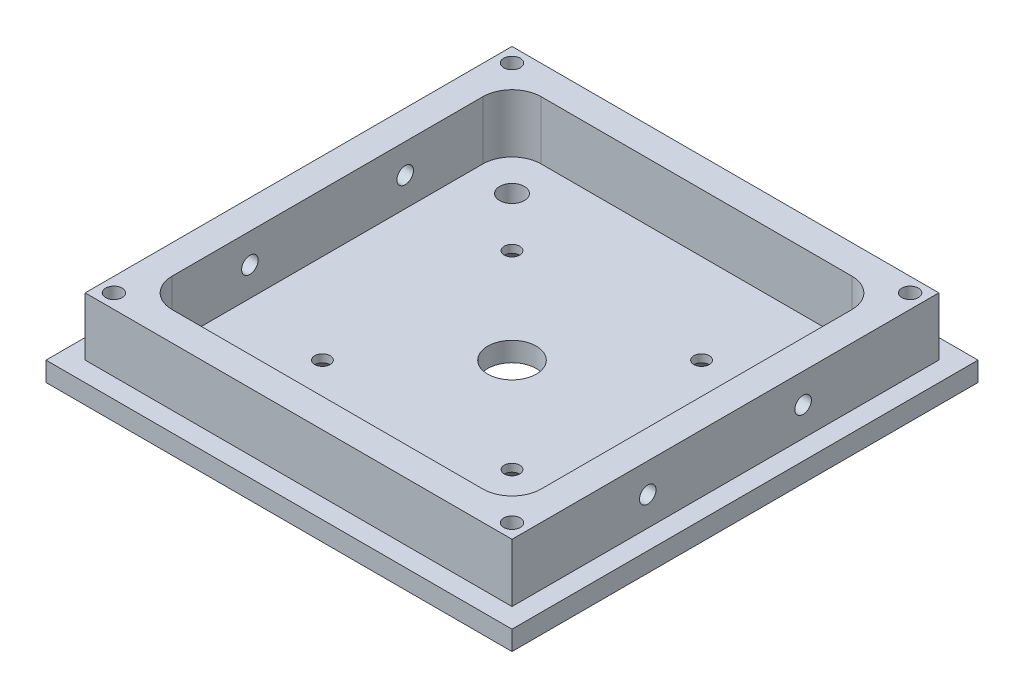
SolidWorks part; units mm, degrees
material "6061-T6 (SS)"
ref_plane "Front Plane" through (0, 0, 0) normal (0, 0, 1) x (1, 0, 0)
ref_plane "Top Plane" through (0, 0, 0) normal (0, 1, 0) x (1, 0, 0)
ref_plane "Right Plane" through (0, 0, 0) normal (1, 0, 0) x (0, 0, -1)
sketch "Sketch1" plane through (0, 0, 0) normal (0, 1, 0) x (1, 0, 0)
  line L1 (-38.1, -38.1) -> (38.1, -38.1)
  line L2 (-38.1, -38.1) -> (-38.1, 38.1)
  line L3 (-38.1, 38.1) -> (38.1, 38.1)
  line L4 (38.1, -38.1) -> (38.1, 38.1)
  line L5 (-38.1, -38.1) -> (38.1, 38.1) construction
  line L6 (-38.1, 38.1) -> (38.1, -38.1) construction
  point P0 (0, 0)
  dimension "D1" = 76.2
  dimension "D2" = 76.2
extrude "Boss-Extrude1" add sketch "Sketch1" along normal blind 3.175
sketch "Sketch2" plane through (0, 3.175, 0) normal (0, 1, 0) x (1, 0, 0)
  line L0 (-38.1, 38.1) -> (-38.1, -38.1) construction
  line L1 (34.8971, -34.8971) -> (-34.8971, -34.8971)
  line L2 (34.8971, -34.8971) -> (34.8971, 34.8971)
  line L3 (34.8971, 34.8971) -> (-34.8971, 34.8971)
  line L4 (-34.8971, -34.8971) -> (-34.8971, 34.8971)
  line L5 (34.8971, -34.8971) -> (-34.8971, 34.8971) construction
  line L6 (34.8971, 34.8971) -> (-34.8971, -34.8971) construction
  line L7 (30.1625, -30.1625) -> (-30.1625, -30.1625)
  line L8 (30.1625, -30.1625) -> (30.1625, 30.1625)
  line L9 (30.1625, 30.1625) -> (-30.1625, 30.1625)
  line L10 (-30.1625, -30.1625) -> (-30.1625, 30.1625)
  line L11 (30.1625, -30.1625) -> (-30.1625, 30.1625) construction
  line L12 (30.1625, 30.1625) -> (-30.1625, -30.1625) construction
  line L14 (38.1, 38.1) -> (-38.1, 38.1) construction
  point P0 (0, 0)
  point P6 (0, 0)
  dimension "D1" = 3.2029
  dimension "D2" = 3.2029
  dimension "D3" = 60.325
extrude "Boss-Extrude2" add sketch "Sketch2" along normal blind 9.525
fillet "Fillet1" radius 4.7625 4 edges at (-30.1625, 7.9375, 30.1625) (30.1625, 7.9375, 30.1625) (30.1625, 7.9375, -30.1625) (-30.1625, 7.9375, -30.1625)
sketch "Sketch3" plane through (0, 3.175, 0) normal (0, 1, 0) x (1, 0, 0)
  circle A0 centre (0, 0) radius 3.9688
  dimension "D1" = 7.9375
sketch "Sketch5" plane through (0, 3.175, 0) normal (0, 1, 0) x (1, 0, 0)
  line L1 (15.5, -15.5) -> (-15.5, -15.5)
  line L2 (15.5, -15.5) -> (15.5, 15.5)
  line L3 (15.5, 15.5) -> (-15.5, 15.5)
  line L4 (-15.5, -15.5) -> (-15.5, 15.5)
  line L5 (15.5, -15.5) -> (-15.5, 15.5) construction
  line L6 (15.5, 15.5) -> (-15.5, -15.5) construction
  line L7 (23.5966, -23.5966) -> (-23.5966, -23.5966)
  line L8 (23.5966, -23.5966) -> (23.5966, 23.5966)
  line L9 (23.5966, 23.5966) -> (-23.5966, 23.5966)
  line L10 (-23.5966, -23.5966) -> (-23.5966, 23.5966)
  line L11 (23.5966, -23.5966) -> (-23.5966, 23.5966) construction
  line L12 (23.5966, 23.5966) -> (-23.5966, -23.5966) construction
  circle A0 centre (-15.5, 15.5) radius 1.2637
  circle A1 centre (15.5, 15.5) radius 1.2637
  circle A2 centre (15.5, -15.5) radius 1.2637
  circle A3 centre (-15.5, -15.5) radius 1.2637
  point P2 (0, 0)
  point P10 (0, 0)
  dimension "D2" = 2.5273
  dimension "D1" = 31
  dimension "D3" = 47.1932
hole_wizard "#39 (0.0995) Diameter Hole1" positions "Sketch7" profile "Sketch6" hole size "#39" standard "ANSI Inch" end condition through all
sketch "Sketch7" plane through (0, 3.175, 0) normal (0, 1, 0) x (1, 0, 0)
  point P0 (15.5, 15.5)
  point P3 (-15.5, 15.5)
  point P6 (-15.5, -15.5)
  point P9 (15.5, -15.5)
  point P12 (-23.5966, 23.5966)
  point P15 (23.5966, 23.5966)
  point P18 (23.5966, -23.5966)
  point P21 (-23.5966, -23.5966)
sketch "Sketch6" plane through (15.5, 3.175, -15.5) normal (1, 0, 0) x (0, 0, 1)
  line L0 (0, 0) -> (0, 3.175)
  line L1 (0, 3.175) -> (1.2636, 3.175)
  line L2 (1.2636, 3.175) -> (1.2636, 0)
  line L5 (1.2636, 0) -> (0, 0)
  line L11 (0, -6.35) -> (0, 107.95) construction
  dimension "Thru Hole Dia." = 2.5273
  dimension "Thru Hole Depth" = 3.175
hole_wizard "#10-32 Tapped Hole1" positions "Sketch17" profile "Sketch15" tap size "#10-32" standard "ANSI Inch" end condition through all
sketch "Sketch17" plane through (0, 3.175, 0) normal (0, 1, 0) x (1, 0, 0)
  point P0 (-23.5966, 23.5966)
  point P3 (23.5966, 23.5966)
  point P6 (23.5966, -23.5966)
  point P9 (-23.5966, -23.5966)
sketch "Sketch15" plane through (-23.5966, 3.175, -23.5966) normal (1, 0, 0) x (0, 0, 1)
  line L0 (0, 0) -> (0, 3.175)
  line L1 (0, 3.175) -> (2.0193, 3.175)
  line L2 (2.0193, 3.175) -> (2.0193, 0)
  line L5 (2.0193, 0) -> (0, 0)
  line L11 (0, -6.35) -> (0, 107.95) construction
  dimension "Thru Tap Drill Dia." = 4.0386
  dimension "Thru Tap Drill Depth" = 3.175
cosmetic thread "Hole Thread3" parameters "D2"=4.826
cosmetic thread "Hole Thread4" parameters "D2"=4.826
cosmetic thread "Hole Thread5" parameters "D2"=4.826
cosmetic thread "Hole Thread6" parameters "D2"=4.826
sketch "Sketch8" plane through (34.8971, 0, 0) normal (1, 0, 0) x (0, 0, -1)
  line L0 (-38.1, 3.175) -> (38.1, 3.175) construction
  point P0 (-12.7, 7.9375)
  dimension "D1" = 4.7625
  dimension "D2" = 12.7
hole_wizard "#6-32 Tapped Hole2" positions "Sketch10" profile "Sketch9" tap size "#6-32" standard "ANSI Inch"
sketch "Sketch10" plane through (34.8971, 0, 0) normal (1, 0, 0) x (0, 0, -1)
  point P0 (-12.7, 7.9375)
cosmetic thread "Hole Thread1" parameters "D1"=4.7346, "D2"=3.5052
sketch "Sketch9" plane through (34.8971, 7.9375, 12.7) normal (0, 1, 0) x (0, 0, -1)
  line L0 (0, 0) -> (0, 11.9887)
  line L1 (0, 11.9887) -> (1.3525, 11.176)
  line L2 (1.3525, 11.176) -> (1.3525, 0)
  line L5 (1.3525, 0) -> (0, 0)
  line L10 (0, 11.9887) -> (-1.3526, 11.176) construction
  line L11 (0, -6.35) -> (0, 107.95) construction
  dimension "Tap Drill Dia." = 2.7051
  dimension "Tap Drill Depth" = 11.176
  dimension "Drill Angle" = 118
mirror "Mirror1" about plane through (0, 0, 0) normal (0, 0, 1) of "#6-32 Tapped Hole2"
mirror "Mirror2" about plane through (0, 0, 0) normal (1, 0, 0) of "Mirror1"
chamfer "Chamfer1" distance 1.905 angle 41 4 edges at (-15.5, 0, -14.2363) (15.5, 0, -14.2364) (15.5, 0, 16.7636) (-15.5, 0, 16.7637) first distance on face at (-15.5, 0, -14.2363) first distance on face at (15.5, 0, -14.2364) first distance on face at (15.5, 0, 16.7636) first distance on face at (-15.5, 0, 16.7637)
sketch "Sketch11" plane through (0, 0, 0) normal (0, -1, 0) x (1, 0, 0)
  circle A0 centre (32.5501, -32.5501) radius 2.032
  dimension "D1" = 4.064
hole_wizard "#6-32 Tapped Hole1" positions "Sketch13" profile "Sketch12" tap size "#6-32" standard "ANSI Inch" end condition through all
sketch "Sketch13" plane through (0, 0, 0) normal (0, -1, 0) x (-1, 0, 0)
  point P0 (-32.5501, 32.5501)
sketch "Sketch12" plane through (32.5501, 0, -32.5501) normal (1, 0, 0) x (0, 0, -1)
  line L0 (0, 0) -> (0, 12.7)
  line L1 (0, 12.7) -> (1.3525, 12.7)
  line L2 (1.3525, 12.7) -> (1.3525, 0)
  line L5 (1.3525, 0) -> (0, 0)
  line L11 (0, -6.35) -> (0, 107.95) construction
  dimension "Thru Tap Drill Dia." = 2.7051
  dimension "Thru Tap Drill Depth" = 12.7
cosmetic thread "Hole Thread2" parameters "D2"=3.5052
extrude "Cut-Extrude1" cut sketch "Sketch3" against normal through all contours A0
pattern_circular "CirPattern1" count 4 over 360 about axis through (0, 0, 0) along (0, 1, 0) of "#6-32 Tapped Hole1"
equation "\"D2@Sketch2\"=\"D1@Sketch2\""
equation "\"D2@Sketch1\"=\"D1@Sketch1\""
